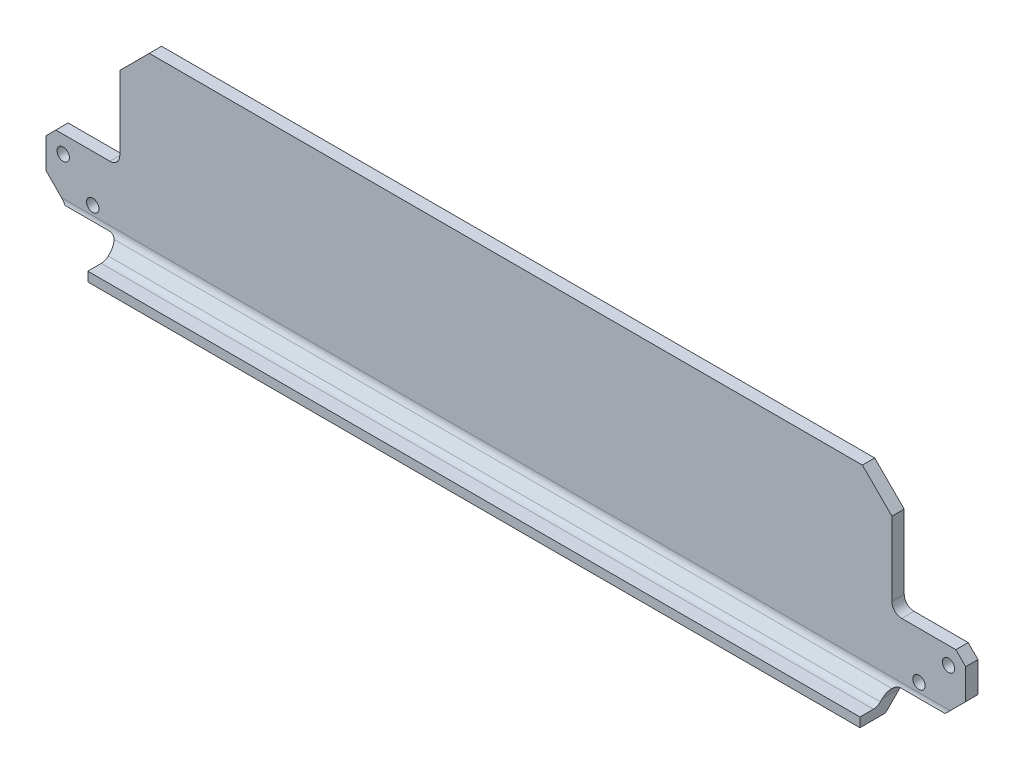
SolidWorks part; units mm, degrees
material "PLA"
ref_plane "Front Plane" through (0, 0, 0) normal (0, 0, 1) x (1, 0, 0)
ref_plane "Top Plane" through (0, 0, 0) normal (0, 1, 0) x (1, 0, 0)
ref_plane "Right Plane" through (0, 0, 0) normal (1, 0, 0) x (0, 0, -1)
sketch "Profile-Sketch" plane through (0, 0, 0) normal (0, 0, 1) x (1, 0, 0)
  line L0 (0, 0) -> (26895.2177, 0) construction
  line L1 (0, 0) -> (0, 26895.2177) construction
  line L2 (-114.3, 9.525) -> (-106.68, 9.525) construction
  line L3 (-114.3, 9.525) -> (-114.3, 17.145) construction
  circle A0 centre (-114.3, 9.525) radius 2 construction
  circle A1 centre (-106.68, 9.525) radius 1.6002 construction
  circle A2 centre (-114.3, 17.145) radius 1.6002 construction
  dimension "D3" = 4
  dimension "D4" = 3.2004
  dimension "D5" = 3.2004
  dimension "D1" = 9.525
  dimension "D2" = 114.3
  dimension "D6" = 7.62
  dimension "D7" = 7.62
sketch "Sketch2" plane through (0, 0, 0) normal (1, 0, 0) x (0, 0, -1)
  line L0 (0, 0) -> (50000, 0) construction
  line L1 (-11.43, 0) -> (-4.826, 0)
  line L2 (-4.826, 0) -> (0, 4.826)
  line L3 (0, -200000) -> (0, 226895.2177) construction
  line L4 (0, 4.826) -> (0, 50.8)
  line L5 (0, 11.525) -> (0, 7.525) construction
  line L6 (0, 50.8) -> (-3.175, 50.8)
  line L7 (-3.175, 50.8) -> (-3.175, 6.1411)
  line L8 (-3.175, 6.1411) -> (-6.9031, 2.413)
  line L9 (-6.9031, 2.413) -> (-11.43, 2.413)
  line L10 (-11.43, 2.413) -> (-11.43, 0)
  dimension "D1" = 3.175
  dimension "D2" = 50.8
  dimension "D3" = 3.175
  dimension "D4" = 2.413
  dimension "D5" = 45
  dimension "D6" = 11.43
  dimension "D7" = 4.826
extrude "Boss-Extrude1" add sketch "Sketch2" along normal mid plane 199.39
sketch "Sketch3" plane through (0, 0, 0) normal (0, 0, 1) x (1, 0, 0)
  line L0 (-99.695, 21.59) -> (-118.745, 21.59)
  line L1 (-99.695, 50.8) -> (-99.695, 6.1411) construction
  line L2 (-118.745, 21.59) -> (-118.745, 6.1411)
  line L3 (-118.745, 6.1411) -> (-99.695, 6.1411)
  line L4 (-200000, 0) -> (226895.2177, 0) construction
  line L5 (-99.695, 21.59) -> (-99.695, 6.1411)
  circle A0 centre (-114.3, 17.145) radius 1.6002 construction
  circle A1 centre (-106.68, 9.525) radius 1.6002 construction
  circle A2 centre (-114.3, 17.145) radius 1.6002
  circle A3 centre (-106.68, 9.525) radius 1.6002
  dimension "D2" = 21.59
  dimension "D3" = 19.05
extrude "Mounting-Plate" add sketch "Sketch3" along normal up to surface (3.175 mm away) up to face at (0, 28.4706, 3.175)
mirror "Mirror1" about plane through (0, 0, 0) normal (1, 0, 0) of "Mounting-Plate"
chamfer "Chamfer1" distance 5.08 angle 45 2 edges at (118.745, 6.1411, 1.5875) (-118.745, 6.1411, 1.5875)
chamfer "Chamfer2" distance 2.54 angle 45 2 edges at (118.745, 21.59, 1.5875) (-118.745, 21.59, 1.5875)
chamfer "Chamfer3" distance 7.62 angle 45 2 edges at (99.695, 50.8, 1.5875) (-99.695, 50.8, 1.5875)
fillet "Fillet1" radius 2.54 4 edges at (-99.695, 6.1411, 1.5875) (99.695, 6.1411, 1.5875) (99.695, 21.59, 1.5875) (-99.695, 21.59, 1.5875)
fillet "Fillet2" radius 2.54 2 edges at (0, 2.413, 6.9031) (0, 6.1411, 3.175)
